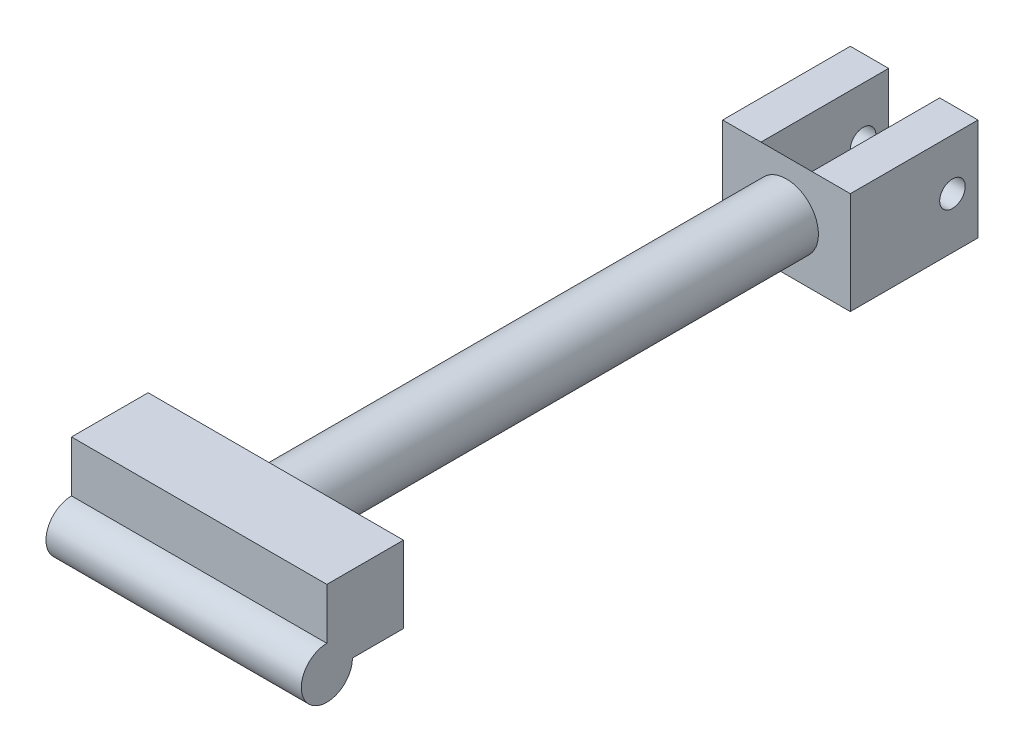
SolidWorks part; units mm, degrees
ref_plane "Ebene vorne" through (0, 0, 0) normal (0, 0, 1) x (1, 0, 0)
ref_plane "Ebene oben" through (0, 0, 0) normal (0, 1, 0) x (1, 0, 0)
ref_plane "Ebene rechts" through (0, 0, 0) normal (1, 0, 0) x (0, 0, -1)
sketch "Skizze1" plane through (0, 0, 0) normal (0, 1, 0) x (1, 0, 0)
  line L1 (-50, 15) -> (50, 15)
  line L2 (-50, 15) -> (-50, -15)
  line L3 (-50, -15) -> (50, -15)
  line L4 (50, 15) -> (50, -15)
  line L5 (-50, 15) -> (50, -15) construction
  line L6 (-50, -15) -> (50, 15) construction
  point P0 (0, 0)
  dimension "D1" = 100
  dimension "D2" = 30
extrude "Aufsatz-Linear austragen1" add sketch "Skizze1" along normal blind 30
sketch "Skizze2" plane through (50, 0, 0) normal (1, 0, 0) x (0, 0, -1)
  circle A0 centre (-15, 0) radius 10
  dimension "D1" = 20
extrude "Aufsatz-Linear austragen2" add sketch "Skizze2" against normal blind 100
sketch "Skizze3" plane through (0, 0, -15) normal (0, 0, -1) x (-1, 0, 0)
  line L0 (-50, 30) -> (50, 30) construction
  line L2 (-50, 30) -> (-50, 0) construction
  circle A0 centre (0, 15) radius 12.5
  dimension "D1" = 15
  dimension "D3" = 25
  dimension "D2" = 50
extrude "Aufsatz-Linear austragen3" add sketch "Skizze3" along normal blind 200
sketch "Skizze4" plane through (0, 0, -215) normal (0, 0, -1) x (-1, 0, 0)
  line L1 (-25, 35) -> (25, 35)
  line L2 (-25, 35) -> (-25, -5)
  line L3 (-25, -5) -> (25, -5)
  line L4 (25, 35) -> (25, -5)
  line L5 (-25, 35) -> (25, -5) construction
  line L6 (-25, -5) -> (25, 35) construction
  point P0 (0, 15)
  dimension "D1" = 50
  dimension "D2" = 40
extrude "Aufsatz-Linear austragen4" add sketch "Skizze4" along normal blind 50
sketch "Skizze6" plane through (0, 0, -265) normal (0, 0, -1) x (-1, 0, 0)
  line L0 (25, 35) -> (-25, 35) construction
  line L1 (-10, -35) -> (10, -35)
  line L2 (-10, -35) -> (-10, 35)
  line L3 (-10, 35) -> (10, 35)
  line L4 (10, -35) -> (10, 35)
  line L5 (-10, -35) -> (10, 35) construction
  line L6 (-10, 35) -> (10, -35) construction
  point P0 (0, 0)
  dimension "D1" = 20
extrude "Schnitt-Linear austragen2" cut sketch "Skizze6" against normal blind 35
chamfer "Fase1" distance 15 angle 45 2 edges at (0, -5, -230) (0, 35, -230)
sketch "Skizze7" plane through (25, 0, 0) normal (1, 0, 0) x (0, 0, -1)
  line L0 (265, 35) -> (265, -5) construction
  line L1 (265, 35) -> (215, 35) construction
  circle A0 centre (255, 15) radius 5
  dimension "D1" = 10
  dimension "D3" = 10
  dimension "D2" = 20
extrude "Schnitt-Linear austragen3" cut sketch "Skizze7" against normal blind 54
